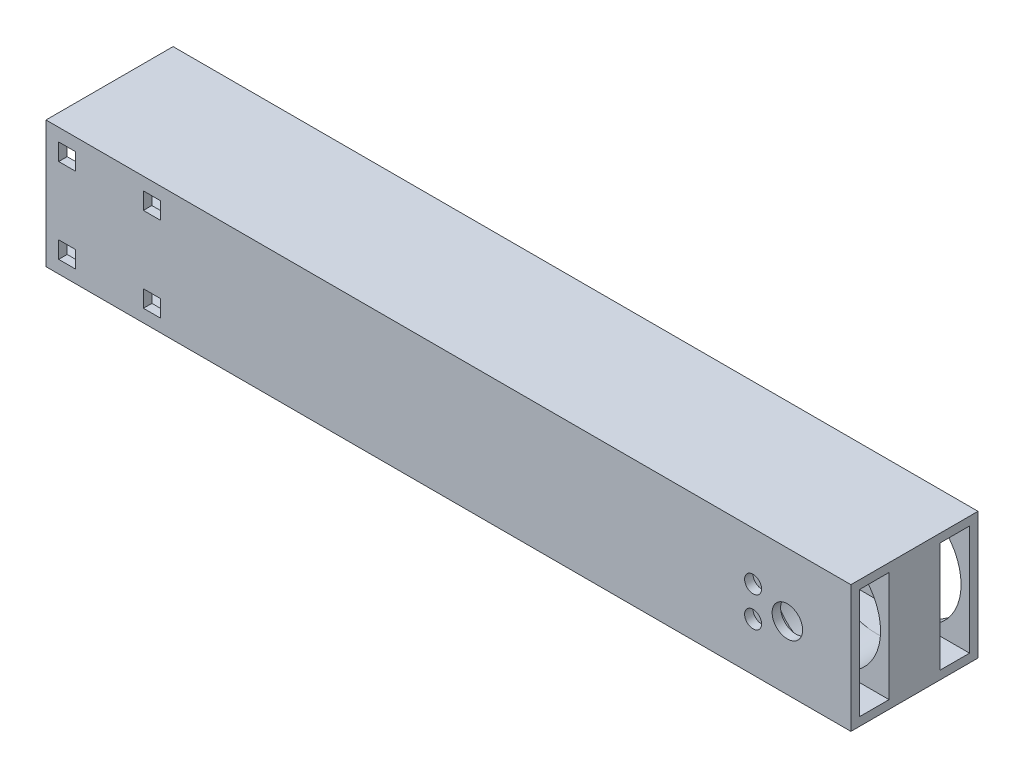
SolidWorks part; units mm, degrees
ref_plane "Front Plane" through (0, 0, 0) normal (0, 0, 1) x (1, 0, 0)
ref_plane "Top Plane" through (0, 0, 0) normal (0, 1, 0) x (1, 0, 0)
ref_plane "Right Plane" through (0, 0, 0) normal (1, 0, 0) x (0, 0, -1)
sketch "Sketch1" plane through (0, 0, 0) normal (1, 0, 0) x (0, 0, -1)
  line L1 (-15, -15) -> (15, -15)
  line L2 (-15, -15) -> (-15, 15)
  line L3 (-15, 15) -> (15, 15)
  line L4 (15, -15) -> (15, 15)
  line L5 (-15, -15) -> (15, 15) construction
  line L6 (-15, 15) -> (15, -15) construction
  line L11 (-5.1844, 5.1844) -> (5.1844, -5.1844) construction
  line L12 (-5.1844, -5.1844) -> (5.1844, 5.1844) construction
  line L13 (-13, 13) -> (-6, 13)
  line L14 (-13, 13) -> (-13, -13)
  line L15 (-13, -13) -> (-6, -13)
  line L16 (-6, 13) -> (-6, -13)
  line L17 (13, 13) -> (6, 13)
  line L18 (13, 13) -> (13, -13)
  line L19 (13, -13) -> (6, -13)
  line L20 (6, 13) -> (6, -13)
  point P0 (0, 0)
  point P7 (0, 0)
  dimension "D1" = 30
  dimension "D2" = 30
  dimension "D3" = 2
  dimension "D4" = 7
  dimension "D5" = 2
  dimension "D6" = 7
  dimension "D7" = 2
  dimension "D8" = 2
extrude "Boss-Extrude3" add sketch "Sketch1" along normal blind 110 and the other way blind 80
sketch "Sketch6" plane through (0, 0, -15) normal (0, 0, -1) x (-1, 0, 0)
  line L0 (-110, -15) -> (-110, 15) construction
  line L2 (-110, 0) -> (80, 0) construction
  line L3 (80, -15) -> (80, 15) construction
  circle A0 centre (-95, 0) radius 13
  point P2 (0, 0)
  dimension "D2" = 26
  dimension "D1" = 15
extrude "Cut-Extrude5" cut sketch "Sketch6" against normal blind 23
sketch "Sketch8" plane through (0, 0, 15) normal (0, 0, 1) x (1, 0, 0)
  line L0 (110, 15) -> (110, -15) construction
  circle A0 centre (95, 0) radius 3.6
  circle A1 centre (86.9069, 3.5812) radius 2
  circle A2 centre (86.9069, -3.5812) radius 2
  dimension "D2" = 7.2
  dimension "D5" = 4
  dimension "D6" = 4
  dimension "D1" = 15
  dimension "D3" = 8.85
  dimension "D4" = 8.85
extrude "Cut-Extrude6" cut sketch "Sketch8" against normal blind 17
sketch "Sketch9" plane through (-80, 0, 0) normal (-1, 0, 0) x (0, 0, 1)
  line L0 (-6, 13) -> (6, 13)
  line L1 (-6, -13) -> (6, -13)
  line L2 (-6, 13) -> (-6, -13)
  line L3 (6, 13) -> (6, -13)
extrude "Cut-Extrude7" cut sketch "Sketch9" against normal blind 106
sketch "Sketch12" plane through (0, 0, 15) normal (0, 0, 1) x (1, 0, 0)
  line L0 (-80, 15) -> (110, 15) construction
  line L1 (-80, 15) -> (-80, -15) construction
  line L2 (-80, 15) -> (-50, 15) construction
  line L3 (-50, 15) -> (-50, -15) construction
  line L5 (-80, -15) -> (110, -15) construction
  line L6 (-77, 8) -> (-73, 8)
  line L7 (-77, 8) -> (-77, 12)
  line L8 (-77, 12) -> (-73, 12)
  line L9 (-73, 8) -> (-73, 12)
  line L10 (-77, 8) -> (-73, 12) construction
  line L11 (-77, 12) -> (-73, 8) construction
  line L12 (-57.0136, 8) -> (-52.9864, 8)
  line L13 (-57.0136, 8) -> (-57.0136, 12)
  line L14 (-57.0136, 12) -> (-52.9864, 12)
  line L15 (-52.9864, 8) -> (-52.9864, 12)
  line L16 (-57.0136, 8) -> (-52.9864, 12) construction
  line L17 (-57.0136, 12) -> (-52.9864, 8) construction
  line L18 (-57, -12) -> (-53, -12)
  line L19 (-57, -12) -> (-57, -8)
  line L20 (-57, -8) -> (-53, -8)
  line L21 (-53, -12) -> (-53, -8)
  line L22 (-57, -12) -> (-53, -8) construction
  line L23 (-57, -8) -> (-53, -12) construction
  line L24 (-77, -12) -> (-73, -12)
  line L25 (-77, -12) -> (-77, -8)
  line L26 (-77, -8) -> (-73, -8)
  line L27 (-73, -12) -> (-73, -8)
  line L28 (-77, -12) -> (-73, -8) construction
  line L29 (-77, -8) -> (-73, -12) construction
  circle A2 centre (-55, 10) radius 2
  circle A3 centre (-75, -10) radius 2
  circle A4 centre (-55, -10) radius 2
  dimension "D3" = 4
  dimension "D7" = 4
  dimension "D9" = 4
  dimension "D11" = 4
  dimension "D2" = 4
  dimension "D4" = 5
  dimension "D5" = 30
  dimension "D6" = 5
  dimension "D8" = 5
  dimension "D10" = 5
  dimension "D12" = 20
  dimension "D13" = 5
  dimension "D14" = 4
extrude "Cut-Extrude8" cut sketch "Sketch12" against normal blind 40 contours L8 L9 L6 L7 | L14 L15 L12 L13 | L20 L21 L18 L19 | L26 L27 L24 L25
